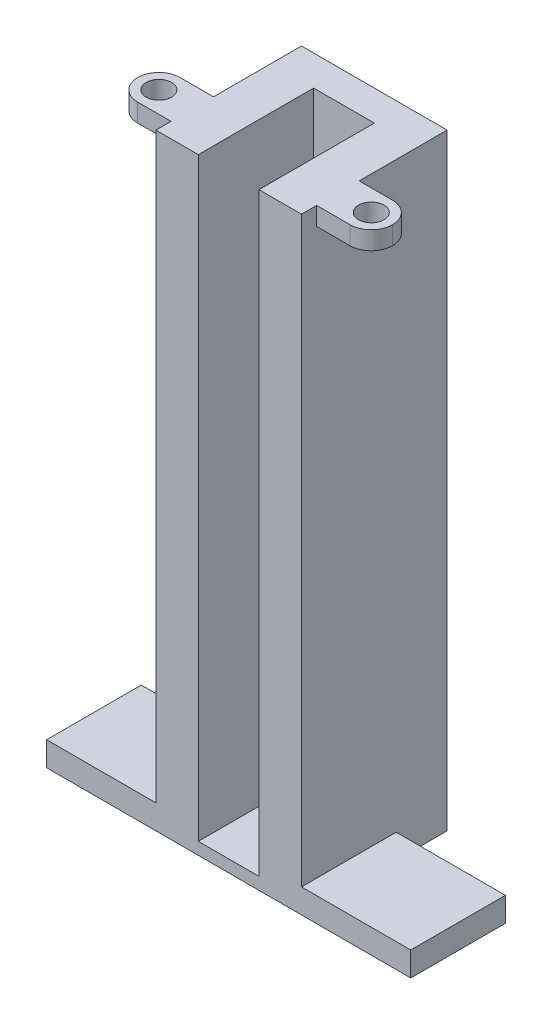
SolidWorks part; units mm, degrees
ref_plane "Front Plane" through (0, 0, 0) normal (0, 0, 1) x (1, 0, 0)
ref_plane "Top Plane" through (0, 0, 0) normal (0, 1, 0) x (1, 0, 0)
ref_plane "Right Plane" through (0, 0, 0) normal (1, 0, 0) x (0, 0, -1)
sketch "Sketch1" plane through (0, 0, 0) normal (0, 1, 0) x (1, 0, 0)
  line L1 (-12, 12) -> (12, 12)
  line L2 (-12, 12) -> (-12, -12)
  line L3 (-12, -12) -> (12, -12)
  line L4 (12, 12) -> (12, -12)
  line L5 (-12, 12) -> (12, -12) construction
  line L6 (-12, -12) -> (12, 12) construction
  point P0 (0, 0)
  dimension "D1" = 24
  dimension "D2" = 24
extrude "Boss-Extrude1" add sketch "Sketch1" along normal blind 100
sketch "Sketch3" plane through (0, 100, 0) normal (0, 1, 0) x (1, 0, 0)
  line L0 (-12, -12) -> (12, -12) construction
  line L1 (-5, -12) -> (5, -12)
  line L2 (-5, -12) -> (-5, 7)
  line L3 (-5, 7) -> (5, 7)
  line L4 (5, -12) -> (5, 7)
  dimension "D2" = 19
  dimension "D3" = 5
extrude "Cut-Extrude1" cut sketch "Sketch3" against normal offset from surface (98 mm away) 2 up to face at (0, 0, 0)
sketch "Sketch6" plane through (-12, 0, 0) normal (-1, 0, 0) x (0, 0, 1)
  line L0 (-12, 100) -> (-12, 0) construction
  line L1 (12, 0) -> (-12, 0)
  line L2 (12, 0) -> (12, 4)
  line L3 (12, 4) -> (-12, 4)
  line L4 (-12, 0) -> (-12, 4)
  dimension "D1" = 4
extrude "Boss-Extrude3" add sketch "Sketch6" along normal blind 18
sketch "Sketch7" plane through (0, 4, 0) normal (0, 1, 0) x (1, 0, 0)
  line L0 (-12, -12) -> (-12, 12) construction
  line L1 (-30, 12) -> (-12, 12)
  line L2 (-30, 12) -> (-30, 3.6)
  line L3 (-30, 3.6) -> (-12, 3.6)
  line L4 (-12, 12) -> (-12, 3.6)
  dimension "D1" = 8.4
extrude "Cut-Extrude3" cut sketch "Sketch7" against normal up to surface (4 mm away) up to face at (-9, 0, 0)
mirror "Mirror2" about plane through (0, 0, 0) normal (1, 0, 0) of "Cut-Extrude3", "Boss-Extrude3"
sketch "Sketch8" plane through (0, 2, 0) normal (0, 1, 0) x (1, 0, 0)
  line L0 (-5, 7) -> (5, 7) construction
  circle A0 centre (0, 2) radius 4
  dimension "D1" = 8
  dimension "D2" = 5
extrude "Cut-Extrude4" cut sketch "Sketch8" against normal blind 1
sketch "Sketch9" plane through (0, 100, 0) normal (0, 1, 0) x (1, 0, 0)
  line L0 (-12, -12) -> (-12, 3.6) construction
  line L1 (-21, -2.5) -> (-12, -2.5)
  line L2 (-21, -2.5) -> (-21, -9.5)
  line L3 (-21, -9.5) -> (-12, -9.5)
  line L4 (-12, -2.5) -> (-12, -9.5)
  line L5 (-21, -2.5) -> (-12, -9.5) construction
  line L6 (-21, -9.5) -> (-12, -2.5) construction
  circle A0 centre (0, 2) radius 4 construction
  circle A1 centre (0, 2) radius 4 construction
  point P0 (-16.5, -6)
  dimension "D1" = 7
  dimension "D2" = 8
  dimension "D3" = 21
extrude "Boss-Extrude4" add sketch "Sketch9" against normal blind 3
fillet "Fillet1" radius 3.5 2 edges at (-21, 98.5, 2.5) (-21, 98.5, 9.5)
sketch "Sketch10" plane through (0, 100, 0) normal (0, 1, 0) x (1, 0, 0)
  circle A0 centre (-17.5, -6) radius 2.1
  dimension "D1" = 4.2
extrude "Cut-Extrude5" cut sketch "Sketch10" against normal up to surface (3 mm away) up to face at (-16.2899, 97, 6)
mirror "Mirror3" about plane through (0, 0, 0) normal (1, 0, 0) of "Boss-Extrude4", "Fillet1", "Cut-Extrude5"
equation "\"rail width\"= 24"
equation "\"system width\"= 125"
equation "\"system depth\"= 250"
equation "\"internal height\"= 100"
equation "\"carriage height\"= 24"
equation "\"belt width\"= 6"
equation "\"worm gear diameter\"= 8"
equation "\"D1@Sketch1\"=\"rail width\""
equation "\"D2@Sketch1\"=\"rail width\""
equation "\"D1@Boss-Extrude1\"=\"internal height\""
equation "\"D1@Sketch3\"=\"worm gear diameter\"+2"
equation "\"D2@Sketch3\"=(\"rail width\"+\"worm gear diameter\")/2+3"
equation "\"D3@Sketch3\"=(\"worm gear diameter\"+2)/2"
equation "\"motor mounting hole spacing\" = 35"
equation "\"motor hole radius\"= 4.2"
equation "\"motor diameter\"= 28"
equation "\"rotor shelf diameter\"= 9"
equation "\"rotor centre from motor centre\"= 8"
equation "\"pin radius\"= 2.7"
equation "\"pin spacing\"= 9"
equation "\"D1@Sketch7\"=\"rail width\"/2-3.6"
equation "\"D1@Sketch8\"=\"worm gear diameter\""
equation "\"D2@Sketch8\"=\"worm gear diameter\"/2+1"
equation "\"D1@Sketch9\"=7"
equation "\"D2@Sketch9\"=\"rotor centre from motor centre\""
equation "\"D3@Sketch9\"=\"motor mounting hole spacing\"/2+3.5"
equation "\"D1@Sketch10\"=\"motor hole radius\""
